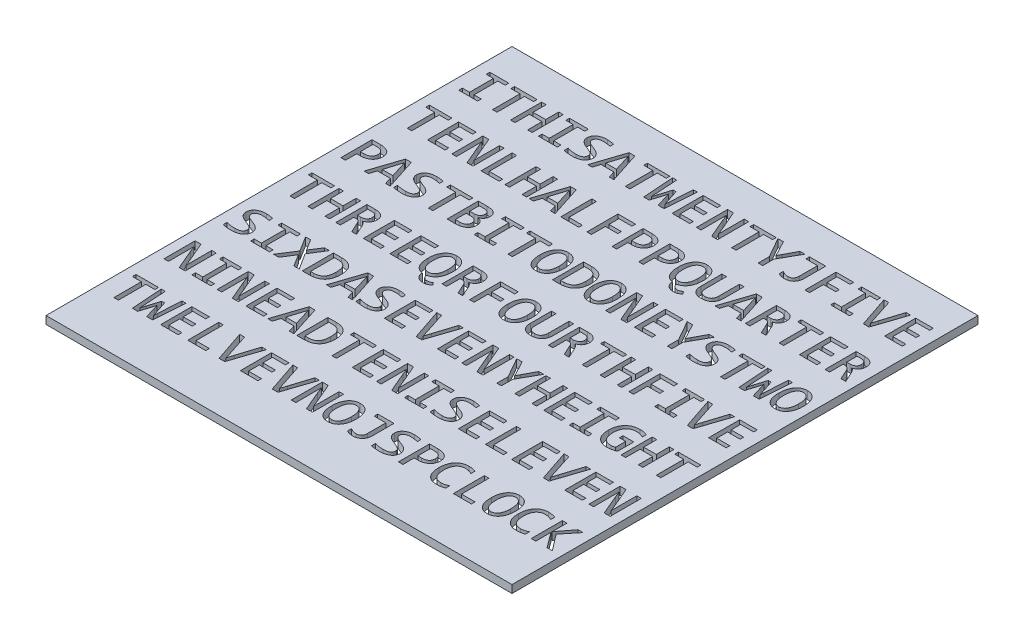
SolidWorks part; units mm, degrees
material "Maple"
ref_plane "Front Plane" through (0, 0, 0) normal (0, 0, 1) x (1, 0, 0)
ref_plane "Top Plane" through (0, 0, 0) normal (0, 1, 0) x (1, 0, 0)
ref_plane "Right Plane" through (0, 0, 0) normal (1, 0, 0) x (0, 0, -1)
sketch "Sketch1" plane through (0, 0, 0) normal (0, 1, 0) x (1, 0, 0)
  line L0 (-95.25, 95.25) -> (95.25, -95.25) construction
  line L1 (-95.25, 95.25) -> (95.25, 95.25)
  line L2 (-95.25, 95.25) -> (-95.25, -95.25)
  line L3 (-95.25, -95.25) -> (95.25, -95.25)
  line L4 (95.25, 95.25) -> (95.25, -95.25)
  dimension "D1" = 190.5
extrude "Boss-Extrude1" add sketch "Sketch1" along normal blind 3.175
sketch "Sketch7" plane through (0, 3.175, 0) normal (0, 1, 0) x (1, 0, 0)
  text T0 "ITHISATWENTYJFIVE\r\nTENLHALFPPQUARTER\r\nPASTBITODONEYSTWO\r\nTHREEQRFOURTHFIVE\r\nSIXDASEVENYHEIGHT\r\nNINEADTENISELEVEN\r\nTWELVEVNOJSPCLOCK" font "Consolas" height 12.7
extrude "Cut-Extrude2" cut sketch "Sketch7" against normal through all
